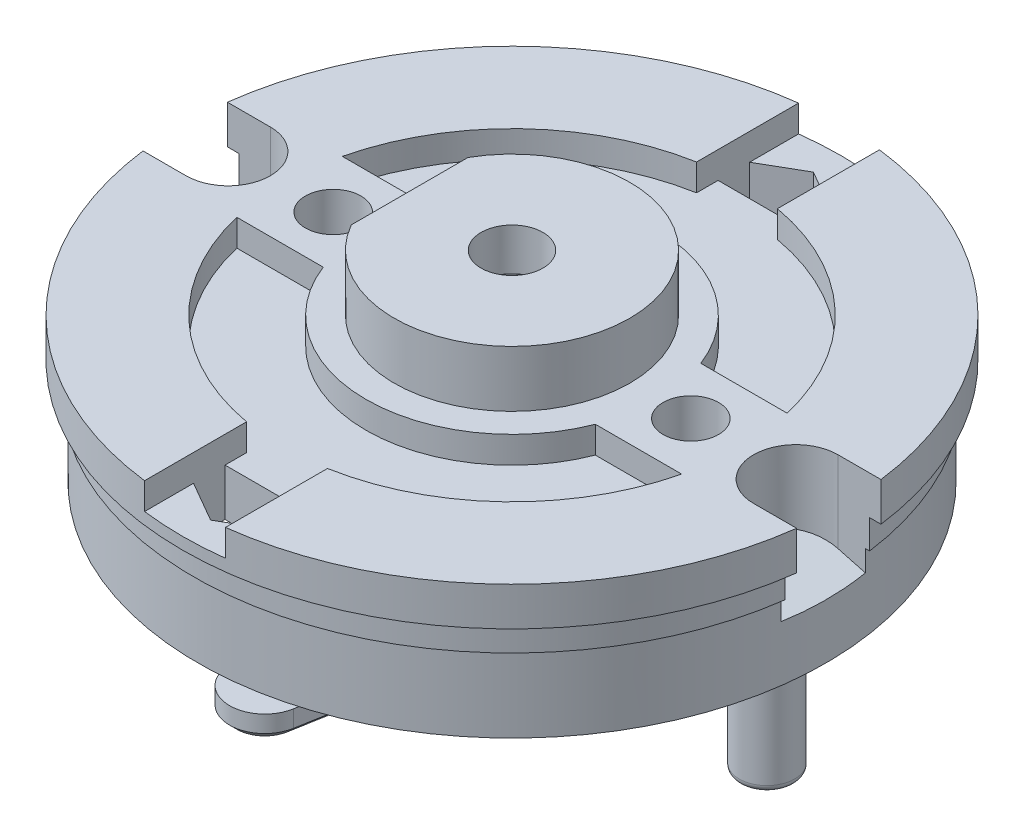
SolidWorks part; units mm, degrees
material "ABS"
ref_plane "Front Plane" through (0, 0, 0) normal (0, 0, 1) x (1, 0, 0)
ref_plane "Top Plane" through (0, 0, 0) normal (0, 1, 0) x (1, 0, 0)
ref_plane "Right Plane" through (0, 0, 0) normal (1, 0, 0) x (0, 0, -1)
sketch "Sketch1" plane through (0, 0, 0) normal (0, 1, 0) x (1, 0, 0)
  circle A0 centre (0, 0) radius 11.8999
  dimension "D1" = 23.7998
extrude "Boss-Extrude1" add sketch "Sketch1" along normal blind 5.207
sketch "Sketch2" plane through (0, 5.207, 0) normal (0, 1, 0) x (1, 0, 0)
  line L0 (-3.6957, 2.1077) -> (-3.6957, -2.1077)
  circle A0 centre (0, 0) radius 4.2545
  dimension "D2" = 8.509
  dimension "D1" = 7.9502
extrude "Boss-Extrude2" add sketch "Sketch2" along normal blind 2.032 contours L0 A0 region at (0.1129, 5.207, 0)
sketch "Sketch4" plane through (0, 5.207, 0) normal (0, 1, 0) x (1, 0, 0)
  line L0 (4.9142, 1.905) -> (8.0322, 1.905)
  line L1 (-4.9142, 1.905) -> (-8.0322, 1.905)
  line L2 (8.0322, -1.905) -> (4.9142, -1.905)
  line L3 (-4.9142, -1.905) -> (-8.0322, -1.905)
  line L4 (-1.4605, 11.8099) -> (-1.4605, 5.0641)
  line L5 (1.4605, 11.8099) -> (1.4605, 5.0641)
  line L6 (-1.4605, -11.8099) -> (-1.4605, -5.0641)
  line L7 (1.4605, -11.8099) -> (1.4605, -5.0641)
  circle A0 centre (0, 0) radius 5.2705
  circle A1 centre (0, 0) radius 8.255
  circle A2 centre (0, 0) radius 11.8999 construction
  circle M1 centre (0, 0) radius 11.8999
  dimension "D6" = 16.51
  dimension "D7" = 10.541
  dimension "D1" = 2.921
  dimension "D2" = 2.921
  dimension "D3" = 1.4605
  dimension "D4" = 3.81
  dimension "D5" = 1.905
extrude "Cut-Extrude1" cut sketch "Sketch4" against normal blind 0.9652 contours A1 L5 L4 M1 | L5 A1 L4 A0 | L0 A1 L5 A0 | L4 A1 L1 A0 | L3 A1 L6 A0 | L7 A1 L2 A0 | L6 A1 L7 A0 | A1 L6 L7 M1 region at (4.5048, 5.207, -4.8141) region at (0, 5.207, -6.7066) region at (0, 5.207, -10.0407) region at (4.5048, 5.207, 4.8141) region at (-4.5048, 5.207, -4.8141) region at (0, 5.207, 6.7066) region at (0, 5.207, 10.0407) region at (-4.5048, 5.207, 4.8141)
sketch "Sketch5" plane through (0, 5.207, 0) normal (0, 1, 0) x (1, 0, 0)
  line L0 (11.8019, 1.524) -> (10.2489, 1.524)
  line L1 (-11.8019, 1.524) -> (-10.2489, 1.524)
  line L2 (10.2489, -1.524) -> (11.8019, -1.524)
  line L3 (-11.8019, -1.524) -> (-10.2489, -1.524)
  arc A0 (1.4605, -11.8099) -> (1.4605, 11.8099) centre (0, 0) ccw construction
  arc A1 (10.2489, 1.524) -> (10.2489, -1.524) centre (10.2489, 0) ccw
  arc A2 (-1.4605, 11.8099) -> (-1.4605, -11.8099) centre (0, 0) ccw construction
  arc A3 (-10.2489, -1.524) -> (-10.2489, 1.524) centre (-10.2489, 0) ccw
  arc A4 (-11.8019, 1.524) -> (-11.8019, -1.524) centre (0, 0) ccw
  arc A5 (11.8019, 1.524) -> (11.8019, -1.524) centre (0, 0) cw
  point P8 (11.8999, 0)
  dimension "D1" = 3.048
  dimension "D2" = 1.524
  dimension "D3" = 1.651
extrude "Cut-Extrude2" cut sketch "Sketch5" against normal blind 3.3528
ref_plane "Plane1" through (0, 0, 0) normal (0, 0, -1) x (-1, 0, 0)
ref_plane "Plane2" through (0, 0, 0) normal (1, 0, 0) x (0, 0, -1)
ref_plane "Plane3" through (11.8019, 0, 0) normal (-1, 0, 0) x (0, 0, 1)
draft "Draft7" type of draft neutral plane draft angle 15 neutral plane "Plane3" faces to draft 1 face at (10.6689, 1.8542, 0) neutral plane through (11.8019, 0, 0) neutral plane normal (-1, 0, 0) reverse direction yes parameters "D1"=15
ref_plane "Plane4" through (-11.8019, 0, 0) normal (-1, 0, 0) x (0, 0, 1)
draft "Draft8" type of draft neutral plane draft angle 15 neutral plane "Plane4" faces to draft 1 face at (-10.6689, 1.8542, 0) neutral plane through (-11.8019, 0, 0) neutral plane normal (-1, 0, 0) parameters "D1"=15
sketch "Sketch7" plane through (0, 7.239, 0) normal (0, 1, 0) x (1, 0, 0)
  line L0 (1.4605, 8.9027) -> (-1.4605, 8.9027)
  line L1 (1.4605, 11.8099) -> (1.4605, 8.1248) construction
  line L2 (-1.4605, 11.8099) -> (-1.4605, 8.1248) construction
  line L3 (-1.4605, 8.9027) -> (-1.4605, 10.0407)
  line L4 (-1.4605, 10.0407) -> (0, 10.8839)
  line L5 (0, 10.8839) -> (1.4605, 10.0407)
  line L7 (1.4605, 10.0407) -> (1.4605, 8.9027)
  line L8 (-1.4605, -8.9027) -> (1.4605, -8.9027)
  line L9 (-1.4605, -11.8099) -> (-1.4605, -8.1248) construction
  line L10 (1.4605, -11.8099) -> (1.4605, -8.1248) construction
  line L11 (1.4605, -8.9027) -> (1.4605, -10.0407)
  line L12 (1.4605, -10.0407) -> (0, -10.8839)
  line L13 (0, -10.8839) -> (-1.4605, -10.0407)
  line L14 (-1.4605, -11.8099) -> (-1.4605, -8.1248) construction
  line L15 (-1.4605, -10.0407) -> (-1.4605, -8.9027)
  line L16 (6.4579, 0) -> (-6.4579, 0)
  circle A0 centre (0, 0) radius 1.1176
  circle A1 centre (-6.4579, 0) radius 1.0033
  circle A2 centre (6.4579, 0) radius 1.0033
  arc A4 (1.4605, 11.8099) -> (-1.4605, 11.8099) centre (0, 0) ccw construction
  arc A5 (-1.4605, -11.8099) -> (1.4605, -11.8099) centre (0, 0) ccw construction
  point P37 (0, 11.8999)
  point P39 (0, -11.8999)
  dimension "D7" = 2.2352
  dimension "D8" = 2.0066
  dimension "D9" = 2.0066
  dimension "D1" = 1.016
  dimension "D2" = 1.9812
  dimension "D3" = 1.016
  dimension "D4" = 1.9812
  dimension "D5" = 120
  dimension "D6" = 120
  dimension "D10" = 12.9159
  dimension "D11" = 6.4579
  dimension "D12" = 0
extrude "Cut-Extrude3" cut sketch "Sketch7" against normal through all contours L15 L13 L12 L11 L8 | A2 | L16 A0 | L16 A0 | A1 | L7 L5 L4 L3 L0 region at (0, 7.239, -9.7015) region at (0, 7.239, 9.7015) region at (-7.4329, 7.239, 0) region at (0, 7.239, 0.4743) region at (0, 7.239, -0.4743) region at (6.4579, 7.239, -0.9749)
sketch "Sketch8" plane through (0, 0, 0) normal (0, -1, 0) x (1, 0, 0)
  circle A0 centre (0, 0) radius 11.8999
  circle A1 centre (0, 0) radius 11.3411
  circle A2 centre (0, 0) radius 11.4935
  circle M6 centre (0, 0) radius 11.8999
  dimension "D1" = 22.6822
  dimension "D2" = 22.987
extrude "Cut-Extrude4" cut sketch "Sketch8" against normal blind 2.7686 contours A2 A1 | A2 M6 region at (-11.5633, 0, 0) region at (-11.461, 0, 0)
extrude "Cut-Extrude5" cut sketch "Sketch8<3>" against normal blind 3.81 contours A2 M6 region at (-11.5633, 0, 0)
sketch "Sketch8<3>" plane through (0, 0, 0) normal (0, -1, 0) x (1, 0, 0) same geometry as "Sketch8"
sketch "Sketch10" plane through (0, 3.81, 0) normal (0, -1, 0) x (1, 0, 0)
  line L0 (-1.4605, -11.8099) -> (-1.4605, -11.4003)
  line L2 (1.4605, -11.8099) -> (1.4605, -11.4003)
  line L4 (-1.27, -11.4231) -> (-1.27, -11.8319)
  line L5 (1.27, -11.8319) -> (1.27, -11.4231)
  line L6 (0, -7.3773) -> (0, 7.3773) construction
  arc A0 (-11.392, -1.524) -> (11.392, -1.524) centre (0, 0) ccw construction
  arc A1 (-1.4605, -11.4003) -> (1.4605, -11.4003) centre (0, 0) ccw
  arc A2 (1.4605, -11.8099) -> (-1.4605, -11.8099) centre (0, 0) cw
  arc M2 (11.392, -1.524) -> (-11.392, -1.524) centre (0, 0) cw
  arc M4 (-11.8019, -1.524) -> (11.8019, -1.524) centre (0, 0) ccw
  dimension "D1" = 2.54
  dimension "D2" = 1.27
extrude "Boss-Extrude12" add sketch "Sketch10" along normal blind 1.651 contours L5 L4 M4 M2 region at (0, 3.81, -11.6736)
sketch "Sketch11" plane through (0, 0, 0) normal (0, -1, 0) x (1, 0, 0)
  line L0 (-8.3185, 0) -> (8.3185, 0) construction
  line L1 (11.3411, 0) -> (11.3411, 11.1451)
  line L2 (7.5311, 0) -> (7.5311, 11.3834)
  line L3 (9.8248, 3.175) -> (-16.4747, 3.175)
  line L4 (9.8248, -3.175) -> (-18.2488, -3.175)
  line L5 (-7.5311, 0) -> (-7.5311, 13.2054)
  line L6 (-11.3411, 0) -> (-11.3411, 12.2429)
  line L7 (6.557, 7.9758) -> (6.2448, 7.6637)
  line L8 (6.096, 7.3045) -> (6.096, 5.9035)
  line L9 (6.9632, 5.5443) -> (7.9758, 6.557)
  line L10 (0, -7.3773) -> (0, 7.3773) construction
  line L11 (0, 0) -> (16.5216, 16.5216)
  line L12 (-6.9632, -5.5443) -> (-7.9758, -6.557)
  line L13 (-6.096, -7.3045) -> (-6.096, -5.9035)
  line L14 (-6.557, -7.9758) -> (-6.2448, -7.6637)
  circle A0 centre (0, 0) radius 10.3251
  circle A1 centre (0, 0) radius 11.3411 construction
  arc A2 (-9.8248, 3.175) -> (-9.8248, -3.175) centre (-10.8754, 0) cw
  arc A3 (6.096, 7.3045) -> (6.2448, 7.6637) centre (6.604, 7.3045) cw
  arc A4 (9.8248, 3.175) -> (9.8248, -3.175) centre (10.8754, 0) ccw
  arc A5 (6.096, 5.9035) -> (6.9632, 5.5443) centre (6.604, 5.9035) ccw
  arc A6 (-6.096, -5.9035) -> (-6.9632, -5.5443) centre (-6.604, -5.9035) ccw
  arc A7 (-6.096, -7.3045) -> (-6.2448, -7.6637) centre (-6.604, -7.3045) cw
  line M1 (1.4605, -8.9027) -> (1.4605, -10.0407)
  line M2 (1.4605, -10.0407) -> (0, -10.8839)
  line M3 (0, -10.8839) -> (-1.4605, -10.0407)
  line M4 (-1.4605, -10.0407) -> (-1.4605, -8.9027)
  line M5 (-1.4605, -8.9027) -> (1.4605, -8.9027)
  circle M6 centre (-6.4579, 0) radius 1.0033
  circle M7 centre (0, 0) radius 1.1176
  circle M8 centre (6.4579, 0) radius 1.0033
  line M9 (-1.4605, 8.9027) -> (-1.4605, 10.0407)
  line M10 (-1.4605, 10.0407) -> (0, 10.8839)
  line M11 (0, 10.8839) -> (1.4605, 10.0407)
  line M12 (1.4605, 10.0407) -> (1.4605, 8.9027)
  line M13 (1.4605, 8.9027) -> (-1.4605, 8.9027)
  dimension "D1" = 1.016
  dimension "D4" = 2.0066
  dimension "D5" = 6.35
  dimension "D3" = 3.81
  dimension "D11" = 0.508
  dimension "D2" = 6.35
  dimension "D6" = 3.81
  dimension "D7" = 3.175
  dimension "D8" = 6.096
  dimension "D9" = 1.0033
  dimension "D10" = 45
  dimension "D12" = 2
extrude "Cut-Extrude6" cut sketch "Sketch11" against normal blind 2.54 contours L8 A3 L7 A0 L5 L3 L11 M11 M12 M13 M9 M10 | A5 L8 L11 L3 L2 L9 | L3 A0 L9 L2 | A4 L3 L2 | A4 L2 L3 L5 A2 L4 M7 M6 M8 | L13 A7 L14 A0 L4 L12 A6 M3 M4 M5 M1 M2 | L3 A2 L5 | L5 A0 L3 region at (7.9971, 0, -2.0794) region at (8.1443, 0, 2.4447) region at (5.8966, 0, 4.2644) region at (8.3926, 0, 4.4862) region at (0.2175, 0, -5.9837) region at (-0.8346, 0, 6.3456) region at (-8.1443, 0, 2.4447) region at (-8.3634, 0, 4.5721)
sketch "Sketch12" plane through (0, 2.54, 0) normal (0, -1, 0) x (1, 0, 0)
  line L0 (0, -7.3773) -> (0, 7.3773) construction
  circle A0 centre (2.794, 5.7023) radius 0.7493
  circle A1 centre (-2.794, -5.7023) radius 0.7493
  dimension "D1" = 1.4986
  dimension "D2" = 2.794
  dimension "D3" = 6.35
  dimension "D4" = 2
extrude "Boss-Extrude13" add sketch "Sketch12" along normal blind 3.556
sketch "Sketch13" plane through (0, 2.54, 0) normal (0, -1, 0) x (1, 0, 0)
  line L0 (0.2735, 7.378) -> (0, 8.9288) construction
  line L1 (0, -7.3773) -> (0, 7.3773) construction
  line L2 (-0.9772, 7.1574) -> (-1.2507, 8.7083)
  line L3 (1.5242, 7.5985) -> (1.2507, 9.1494)
  line L5 (-8.3185, 0) -> (8.3185, 0) construction
  line L6 (-0.2735, -7.378) -> (0, -8.9288) construction
  line L7 (0.9772, -7.1574) -> (1.2507, -8.7083)
  line L8 (-1.5242, -7.5985) -> (-1.2507, -9.1494)
  arc A0 (-0.9772, 7.1574) -> (1.5242, 7.5985) centre (0.2735, 7.378) ccw
  arc A1 (1.2507, 9.1494) -> (-1.2507, 8.7083) centre (0, 8.9288) ccw
  arc A2 (0.9772, -7.1574) -> (-1.5242, -7.5985) centre (-0.2735, -7.378) ccw
  arc A3 (-1.2507, -9.1494) -> (1.2507, -8.7083) centre (0, -8.9288) ccw
  point P4 (0.1367, 8.1534)
  point P16 (-0.1367, -8.1534)
  dimension "D2" = 1.5748
  dimension "D1" = 2.54
  dimension "D3" = 170
  dimension "D4" = 8.1534
  dimension "D5" = 2
extrude "Boss-Extrude14" add sketch "Sketch13" along normal blind 5.3086
sketch "Sketch14" plane through (0, 2.54, 0) normal (0, 1, 0) x (1, 0, 0)
  line L0 (1.2942, -8.9027) -> (-1.2697, -8.9027)
  line L1 (-1.2942, 8.9027) -> (1.2697, 8.9027)
  arc A0 (1.2942, -8.9027) -> (-1.2697, -8.9027) centre (0.0122, -9.0755) cw
  arc A1 (1.2697, 8.9027) -> (-1.2942, 8.9027) centre (-0.0122, 9.0614) ccw
  arc A2 (1.2697, 8.9027) -> (-1.2507, 9.1494) centre (0, 8.9288) ccw construction
extrude "Cut-Extrude7" cut sketch "Sketch14" against normal blind 4.445
sketch "Sketch15" plane through (0, 2.54, 0) normal (0, -1, 0) x (1, 0, 0)
  line L0 (0, 0) -> (2.794, 5.7023)
  line L1 (0, 0) -> (5.7023, -2.794)
  line L2 (0, 0) -> (-2.794, -5.7023)
  line L3 (0, 0) -> (-5.7023, 2.794)
  circle A0 centre (-5.7023, 2.794) radius 0.5715
  circle A1 centre (5.7023, -2.794) radius 0.5715
  dimension "D2" = 1.143
  dimension "D3" = 1.143
  dimension "D1" = 4
extrude "Boss-Extrude15" add sketch "Sketch15" along normal blind 1.778 contours A0 | A1 region at (5.8277, 2.54, -2.253) region at (-6.2433, 2.54, 2.9194)
sketch "Sketch16" plane through (0, 2.54, 0) normal (0, -1, 0) x (1, 0, 0)
  circle A0 centre (0, 0) radius 3.0099
  dimension "D1" = 6.0198
extrude "Cut-Extrude8" cut sketch "Sketch16" against normal blind 3.175
sketch "Sketch17" plane through (0, 2.54, 0) normal (0, -1, 0) x (1, 0, 0)
  circle A0 centre (0, 0) radius 4.0005
  dimension "D1" = 8.001
extrude "Cut-Extrude9" cut sketch "Sketch17" against normal blind 0.635
sketch "Sketch18" plane through (0, 0, 0) normal (0, -1, 0) x (1, 0, 0)
  circle A0 centre (-9.2075, 0) radius 1.0033
  circle A1 centre (9.2075, 0) radius 1.0033
  dimension "D1" = 2.0066
  dimension "D2" = 2.0066
  dimension "D3" = 18.415
  dimension "D4" = 9.2075
extrude "Boss-Extrude16" add sketch "Sketch18" along normal blind 4.445
sketch "Sketch19" plane through (0, 5.715, 0) normal (0, -1, 0) x (1, 0, 0)
  line L0 (1.9311, 0.3817) -> (2.6395, 0.3817)
  line L1 (1.2961, 1.4816) -> (1.6503, 2.0951)
  line L2 (1.2961, -1.4816) -> (1.6503, -2.0951)
  line L3 (1.9311, -0.3817) -> (2.6395, -0.3817)
  line L4 (-0.635, -1.8633) -> (-0.9892, -2.4768)
  line L5 (0.635, -1.8633) -> (0.9892, -2.4768)
  line L6 (-1.9311, -0.3817) -> (-2.6395, -0.3817)
  line L7 (0.635, 1.8633) -> (0.9892, 2.4768)
  line L8 (-0.635, 1.8633) -> (-0.9892, 2.4768)
  line L9 (-1.2961, -1.4816) -> (-1.6503, -2.0951)
  line L10 (-1.2961, 1.4816) -> (-1.6503, 2.0951)
  line L11 (-1.9311, 0.3817) -> (-2.6395, 0.3817)
  line L12 (0, 0) -> (0, 1.1176)
  arc A0 (0.635, 1.8633) -> (-0.635, 1.8633) centre (0, 0) ccw
  arc A1 (1.9311, 0.3817) -> (1.2961, 1.4816) centre (0, 0) ccw
  arc A3 (2.6395, 0.3817) -> (1.6503, 2.0951) centre (0, 0) ccw
  arc A4 (0.9892, 2.4768) -> (-0.9892, 2.4768) centre (0, 0) ccw
  arc A5 (1.2961, -1.4816) -> (1.9311, -0.3817) centre (0, 0) ccw
  arc A6 (1.6503, -2.0951) -> (2.6395, -0.3817) centre (0, 0) ccw
  arc A7 (-0.635, -1.8633) -> (0.635, -1.8633) centre (0, 0) ccw
  arc A8 (-0.9892, -2.4768) -> (0.9892, -2.4768) centre (0, 0) ccw
  arc A9 (-1.9311, -0.3817) -> (-1.2961, -1.4816) centre (0, 0) ccw
  arc A10 (-2.6395, -0.3817) -> (-1.6503, -2.0951) centre (0, 0) ccw
  arc A11 (-1.2961, 1.4816) -> (-1.9311, 0.3817) centre (0, 0) ccw
  arc A12 (-1.6503, 2.0951) -> (-2.6395, 0.3817) centre (0, 0) ccw
  circle A13 centre (0, 0) radius 1.1176 construction
  point P4 (-0.4619, 0.2667)
  point P10 (0.8716, 2.5764)
  point P11 (0.4619, 0.2667)
  point P12 (-0.8716, 2.5764)
  dimension "D1" = 60
  dimension "D2" = 3.937
  dimension "D3" = 2.667
  dimension "D4" = 6
  dimension "D5" = 30
  dimension "D6" = 1.27
  dimension "D7" = 0.635
extrude "Boss-Extrude17" add sketch "Sketch19" along normal up to surface (2.54 mm away) contours L7 A4 L8 A0 | L0 A3 L1 A1 | L2 A6 L3 A5 | L10 A12 L11 A11 | L4 A8 L5 A7 | L6 A10 L9 A9 region at (1.9859, 5.715, 1.1466) region at (1.9859, 5.715, -1.1466) region at (0, 5.715, -2.2931) region at (-1.9859, 5.715, -1.1466) region at (0, 5.715, 2.2931) region at (-1.9859, 5.715, 1.1466) up to face at (0, 3.175, -4.0005)
ref_plane "Plane5" through (0, 0, 0) normal (0.866, 0, -0.5) x (-0.5, 0, -0.866)
sketch "Sketch21" plane through (0, 0, 0) normal (0.866, 0, -0.5) x (-0.5, 0, -0.866)
  line L7 (-1.9311, 3.175) -> (-1.9311, 5.715) construction
  line L8 (-1.9311, 5.336) -> (-1.9311, 3.177)
  arc A0 (-1.9311, 5.336) -> (-1.9311, 3.177) centre (7.321, 4.2565) ccw
  dimension "D1" = 9.3149
  dimension "D2" = 2.159
ref_axis "Axis1" through (0, 5.715, 0) along (0, 1, 0)
revolve "Cut-Revolve3" cut sketch "Sketch21" angle 360 about axis through (0, 5.715, 0) along (0, 1, 0) region at (0.9781, 4.2565, 1.6942)
sketch "Sketch22" plane through (0, -2.7686, 0) normal (0, -1, 0) x (1, 0, 0)
  circle A0 centre (0, -8.9288) radius 0.6346
  dimension "D1" = 1.2691
extrude "Boss-Extrude18" add sketch "Sketch22" along normal blind 1.905
fillet "Fillet1" radius 0.254 3 edges at (0, -4.6736, -9.5634) (9.2075, -4.445, -1.0033) (-9.2075, -4.445, -1.0033)
chamfer "Chamfer1" distance 0.254 angle 45 8 edges at (-1.114, -2.7686, 7.9329) (-0.2205, -2.7686, 10.1795) (1.3874, -2.7686, 8.3739) (0.494, -2.7686, 6.1273) (0.2205, -2.7686, -10.1795) (-1.3874, -2.7686, -8.3739) (-0.494, -2.7686, -6.1273) (1.114, -2.7686, -7.9329)
sketch "Sketch23" plane through (0, 2.54, 0) normal (0, -1, 0) x (1, 0, 0)
  arc A0 (1.4656, 10.2206) -> (2.9081, 9.5269) centre (2.5146, 10.5553) ccw
  arc A1 (6.557, 7.9758) -> (1.0629, 10.2702) centre (0, 0) ccw construction
  arc A2 (3.2321, 9.8062) -> (2.9081, 9.5269) centre (2.6826, 10.1161) cw
  arc A4 (1.4656, 10.2206) -> (3.2321, 9.8062) centre (0, 0) cw
extrude "Boss-Extrude19" add sketch "Sketch23" along normal up to surface (2.54 mm away) up to face at (-9.2075, 0, 1.0033)
mirror "Mirror1" about plane through (0, 0, 0) normal (1, 0, 0) of "Boss-Extrude19"
pattern_circular "CirPattern1" count 2 over 360 about axis through (0, 2.7686, 0) along (0, -1, 0) of "Mirror1", "Boss-Extrude19"
